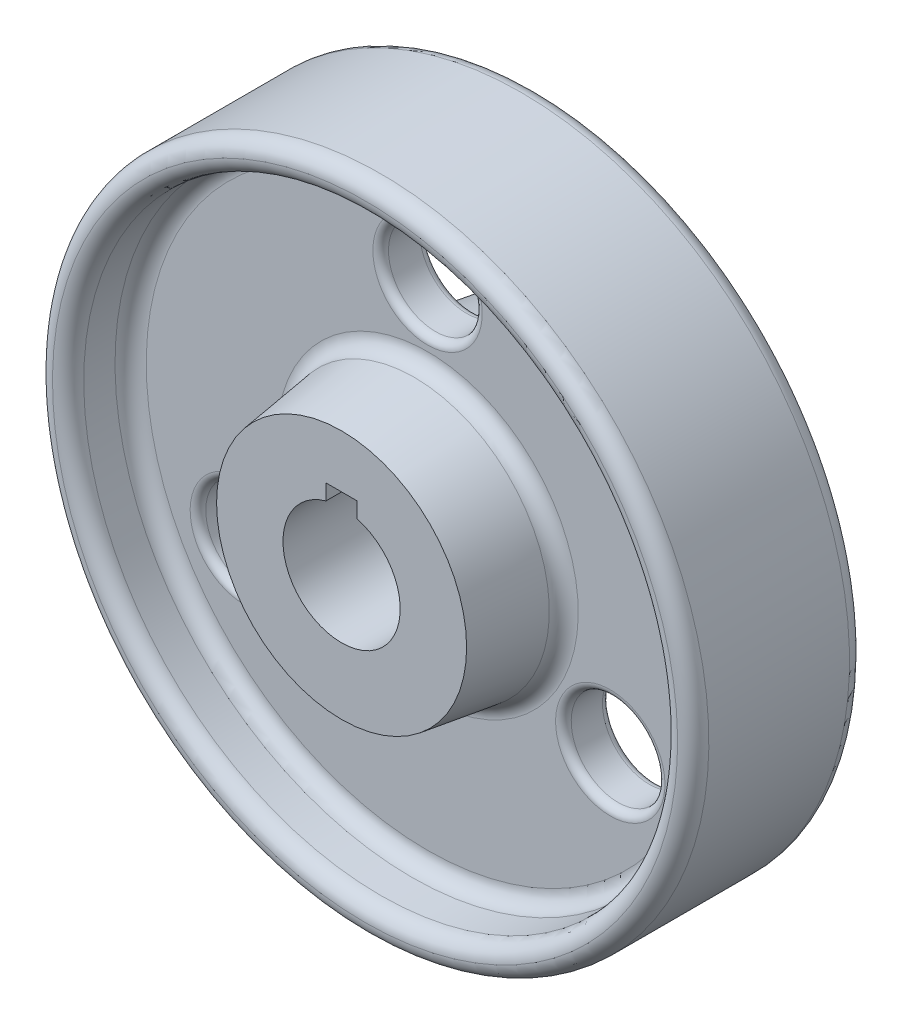
SolidWorks part; units mm, degrees
material "AISI 1020"
ref_plane "Plane1" through (0, 0, 0) normal (0, 0, 1) x (1, 0, 0)
ref_plane "Plane2" through (0, 0, 0) normal (0, 1, 0) x (1, 0, 0)
ref_plane "Plane3" through (0, 0, 0) normal (1, 0, 0) x (0, 0, -1)
sketch "Esquisse1" plane through (0, 0, 0) normal (1, 0, 0) x (0, 0, -1)
  line L0 (-37.9095, 0) -> (37.9095, 0) construction
  line L1 (-22.225, 0) -> (-22.225, 25.4)
  line L2 (-22.225, 25.4) -> (-4.7625, 27.8542)
  line L3 (-4.7625, 27.8542) -> (-4.7625, 60.325)
  line L4 (-4.7625, 60.325) -> (-17.4625, 60.325)
  line L5 (-17.4625, 60.325) -> (-17.4625, 66.675)
  line L6 (-17.4625, 66.675) -> (17.4625, 66.675)
  line L7 (17.4625, 66.675) -> (17.4625, 60.325)
  line L8 (17.4625, 60.325) -> (4.7625, 60.325)
  line L9 (4.7625, 60.325) -> (4.7625, 27.8542)
  line L10 (4.7625, 27.8542) -> (22.225, 25.4)
  line L11 (22.225, 25.4) -> (22.225, 0)
  line L12 (-22.225, 0) -> (22.225, 0)
  line L13 (22.225, 25.4) -> (3.8922, 25.4) construction
  point P3 (0, 0)
  point P4 (0, 0)
  dimension "D1" = 34.925
  dimension "D2" = 44.45
  dimension "D3" = 9.525
  dimension "D4" = 8
  dimension "D5" = 133.35
  dimension "D6" = 120.65
  dimension "D7" = 50.8
revolve "Révolution1" add sketch "Esquisse1" angle 360 about L0
sketch "Esquisse2" plane through (0, 0, 0) normal (0, 0, 1) x (1, 0, 0)
  circle A0 centre (0, 0) radius 42.8625 construction
  circle A1 centre (0, 42.8625) radius 9.525
  point P5 (0, 0)
  dimension "D1" = 85.725
  dimension "D2" = 19.05
extrude "Enlèv. mat.-Extru.5" cut sketch "Esquisse2" against normal through all and the other way through all
fillet "Congé1" radius 1.5875 2 edges at (0, 33.3375, 4.7625) (0, 52.3875, -4.7625)
pattern_circular "Répétition circulaire3" count 3 over 360 about axis through (0, 0, 37.9095) along (0, 0, 1) of "Congé1", "Enlèv. mat.-Extru.5"
fillet "Congé2" radius 3.175 8 edges at (0, -60.325, 17.4625) (0, -66.675, 17.4625) (0, -66.675, -17.4625) (0, -60.325, -17.4625) (0, -60.325, 4.7625) (0, -60.325, -4.7625) (0, -27.8542, 4.7625) (0, -27.8542, -4.7625)
sketch "Esquisse3" plane through (0, 0, -22.225) normal (0, 0, -1) x (-1, 0, 0)
  line L1 (-3.175, 14.6501) -> (3.175, 14.6501)
  line L2 (-3.175, 14.6501) -> (-3.175, 11.4751)
  line L4 (3.175, 14.6501) -> (3.175, 11.4751)
  arc A0 (-3.175, 11.4751) -> (3.175, 11.4751) centre (0, 0) ccw
  dimension "D2" = 11.9062
  dimension "D1" = 6.35
  dimension "D3" = 3.175
extrude "Enlèv. mat.-Extru.7" cut sketch "Esquisse3" against normal through all
